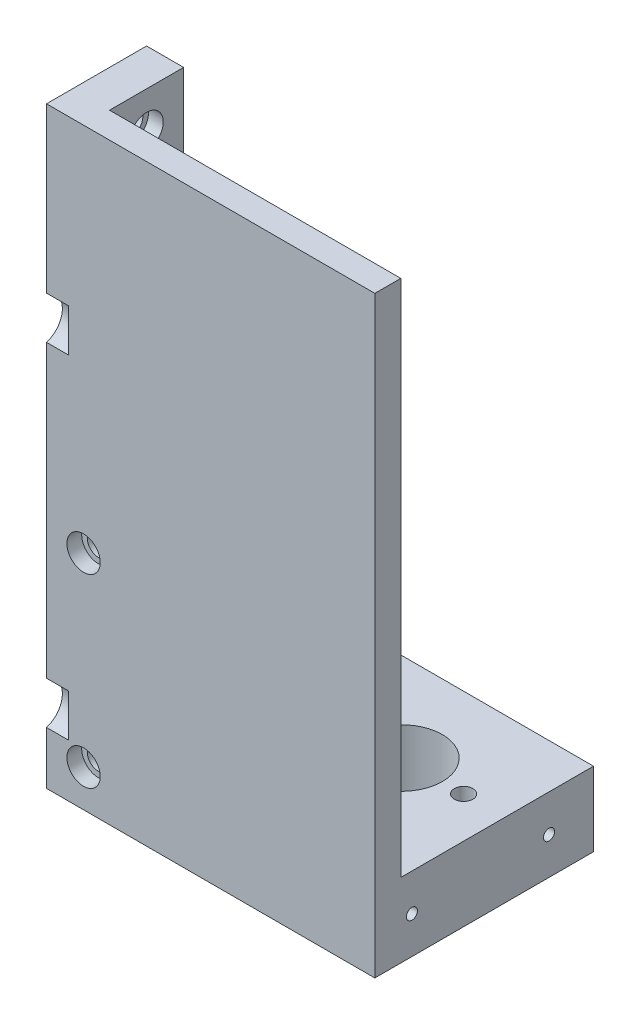
SolidWorks part; units mm, degrees
ref_plane "前视基准面" through (0, 0, 0) normal (0, 0, 1) x (1, 0, 0)
ref_plane "上视基准面" through (0, 0, 0) normal (0, 1, 0) x (1, 0, 0)
ref_plane "右视基准面" through (0, 0, 0) normal (1, 0, 0) x (0, 0, -1)
other "Configuration Table"
sketch "草图1" plane through (0, 0, 0) normal (0, 1, 0) x (1, 0, 0)
  line L0 (-8.375, 0) -> (8.375, 0)
  line L33 (-17.5, -17.5) -> (17.5, -17.5)
  line L34 (-17.5, -17.5) -> (-17.5, 17.5)
  line L35 (-17.5, 17.5) -> (17.5, 17.5)
  line L36 (17.5, -17.5) -> (17.5, 17.5)
  line L37 (-17.5, -17.5) -> (17.5, 17.5) construction
  line L38 (-17.5, 17.5) -> (17.5, -17.5) construction
  line L40 (-17.5, 17.5) -> (-20.4, 17.5)
  line L41 (-17.5, 17.5) -> (-17.5, -17.5)
  line L42 (-17.5, -17.5) -> (-20.4, -17.5)
  line L43 (-20.4, 17.5) -> (-20.4, -17.5)
  circle A0 centre (0, 0) radius 5.5
  circle A1 centre (-8.375, 0) radius 2
  circle A2 centre (-8.375, 0) radius 1.25
  circle A3 centre (8.375, 0) radius 2
  circle A4 centre (8.375, 0) radius 1.25
  circle A5 centre (0, -10.9) radius 1.25
  circle A6 centre (0, -10.9) radius 2
  point P0 (-90.6464, 22.0667)
  point P11 (0, 0)
  dimension "D1" = 11
  dimension "D2" = 35
  dimension "D3" = 16.75
  dimension "D4" = 2.5
  dimension "D5" = 4
  dimension "D6" = 2.9
extrude "凸台-拉伸1" add sketch "草图1" along normal blind 10 contours L40 L43 L42 L34 | L36 L35 L34 L33 | A0 | A2 | A4 | A5 region at (-18.95, 0, 0)
extrude "切除-拉伸1" cut sketch "草图1<16>" along normal offset from surface (7 mm away) 3 contours A1 | A6 | A3 up to face at (-1.45, 10, 0)
sketch "草图1<16>" plane through (0, 0, 0) normal (0, 1, 0) x (1, 0, 0) same geometry as "草图1"
sketch "草图2" plane through (-20.4, 0, 0) normal (-1, 0, 0) x (0, 0, 1)
  line L0 (-17.5, 0) -> (17.5, 0) construction
  line L1 (-12, 0) -> (-7.1, 0)
  line L2 (-12, 0) -> (-12, 10)
  line L3 (-12, 10) -> (-7.1, 10)
  line L4 (-7.1, 0) -> (-7.1, 10)
  line L5 (-17.5, 10) -> (17.5, 10) construction
  line L7 (17.5, 0) -> (13.1, 0)
  line L8 (17.5, 0) -> (17.5, 10)
  line L9 (17.5, 10) -> (13.1, 10)
  line L10 (13.1, 0) -> (13.1, 10)
  dimension "D1" = 4.9
  dimension "D2" = 4.4
extrude "凸台-拉伸2" add sketch "草图2" along normal blind 10 contours L2 L3 L4 L1 | L8 L9 L10 L7
sketch "草图3" plane through (0, 10, 0) normal (0, 1, 0) x (1, 0, 0)
  line L0 (17.5, -17.5) -> (17.5, 17.5) construction
  line L1 (17.5, -14) -> (-30.4, -14)
  line L2 (17.5, -14) -> (17.5, -17.5)
  line L3 (17.5, -17.5) -> (-30.4, -17.5)
  line L4 (-30.4, -14) -> (-30.4, -17.5)
  line L5 (17.5, -17.5) -> (-30.4, -17.5) construction
  dimension "D1" = 3.5
  dimension "D2" = 47.9
extrude "凸台-拉伸3" add sketch "草图3" along normal blind 70
sketch "草图4" plane through (-20.4, 0, 0) normal (-1, 0, 0) x (0, 0, 1)
  line L1 (-17.5, 0) -> (-12, 0)
  line L2 (-17.5, 0) -> (-17.5, 10)
  line L3 (-17.5, 10) -> (-12, 10)
  line L4 (-12, 0) -> (-12, 10)
extrude "切除-拉伸7" cut sketch "草图4" against normal through all
sketch "草图6" plane through (0, 10, 0) normal (0, 1, 0) x (1, 0, 0)
  line L0 (-20.4, 7.1) -> (-20.4, -13.1) construction
  line L1 (-30.4, -13.1) -> (-20.4, -13.1)
  line L2 (-30.4, -13.1) -> (-30.4, -14)
  line L3 (-30.4, -14) -> (-20.4, -14)
  line L4 (-20.4, -13.1) -> (-20.4, -14)
  line L5 (17.5, -14) -> (-30.4, -14) construction
extrude "切除-拉伸10" cut sketch "草图6" against normal through all contours L3 L4 L1 L2
sketch "草图8" plane through (0, 10, 0) normal (0, 1, 0) x (1, 0, 0)
  line L0 (-30.4, -17.5) -> (17.5, -17.5) construction
  line L1 (17.5, 12) -> (13.9, 12)
  line L2 (17.5, 12) -> (17.5, -17.5)
  line L3 (17.5, -17.5) -> (13.9, -17.5)
  line L4 (13.9, 12) -> (13.9, -17.5)
  line L5 (17.5, -14) -> (17.5, 12) construction
  line L6 (-30.4, 12) -> (17.5, 12) construction
  dimension "D1" = 3.6
extrude "切除-拉伸9" cut sketch "草图8" against normal through all both and the other way through all
sketch "草图9" plane through (0, 0, 14) normal (0, 0, -1) x (-1, 0, 0)
  line L1 (30.4, 80) -> (25.4, 80)
  line L2 (30.4, 80) -> (30.4, 70)
  line L3 (30.4, 70) -> (25.4, 70)
  line L4 (25.4, 80) -> (25.4, 70)
  dimension "D1" = 5
  dimension "D2" = 10
extrude "凸台-拉伸8" add sketch "草图9" along normal blind 10
sketch "草图10" plane through (0, 0, -12) normal (0, 0, -1) x (-1, 0, 0)
  line L0 (30.4, 0) -> (30.4, 10) construction
  circle A0 centre (25.4, 5) radius 2.25
  circle A1 centre (25.4, 5) radius 1.5
  circle A2 centre (25.4, 30) radius 2.25
  circle A3 centre (25.4, 30) radius 1.5
  point P10 (30.4, 5)
  dimension "D1" = 4.5
  dimension "D2" = 3
  dimension "D3" = 5
  dimension "D4" = 25
extrude "切除-拉伸11" cut sketch "草图10" against normal through all contours A1 | A3
extrude "切除-拉伸12" cut sketch "草图10<3>" against normal blind 2 contours A0
sketch "草图10<3>" plane through (0, 0, -12) normal (0, 0, -1) x (-1, 0, 0) same geometry as "草图10"
extrude "切除-拉伸13" cut sketch "草图10<5>" along normal blind 2 from surface contours A0 | A2 starting at face at (-26.9, 5, 17.5)
sketch "草图10<5>" plane through (0, 0, -12) normal (0, 0, -1) x (-1, 0, 0) same geometry as "草图10"
sketch "草图11" plane through (-25.4, 0, 0) normal (1, 0, 0) x (0, 0, -1)
  line L2 (-4, 80) -> (-14, 70) construction
  circle A0 centre (-9, 75) radius 1.5
  circle A1 centre (-9, 75) radius 2.25
  dimension "D1" = 3
  dimension "D2" = 4.5
extrude "切除-拉伸14" cut sketch "草图11" against normal blind 2 contours A1
extrude "切除-拉伸15" cut sketch "草图11<3>" against normal through all contours A0
sketch "草图11<3>" plane through (-25.4, 0, 0) normal (1, 0, 0) x (0, 0, -1) same geometry as "草图11"
sketch "草图12" plane through (13.9, 0, 0) normal (1, 0, 0) x (0, 0, -1)
  circle A0 centre (6, 5) radius 0.75
  circle A1 centre (-12.5, 5) radius 0.75
  dimension "D1" = 1.5
extrude "切除-拉伸16" cut sketch "草图12" against normal blind 4 contours A0 | A1
sketch "草图13" plane through (0, 0, -12) normal (0, 0, -1) x (-1, 0, 0)
  circle A0 centre (15.1, 5) radius 0.75
  dimension "D1" = 1.5
extrude "切除-拉伸17" cut sketch "草图13" against normal blind 4 contours A0
sketch "草图14" plane through (13.9, 0, 0) normal (1, 0, 0) x (0, 0, -1)
  circle A0 centre (-18.3586, 54.999) radius 3
  circle A1 centre (-18.3586, 9.999) radius 3
  point P4 (0, 0)
  point P5 (0, 0)
  dimension "D1" = 6
extrude "切除-拉伸18" cut sketch "草图14" along normal blind 3 from surface starting at face at (-30.4, 75, 7.5)
